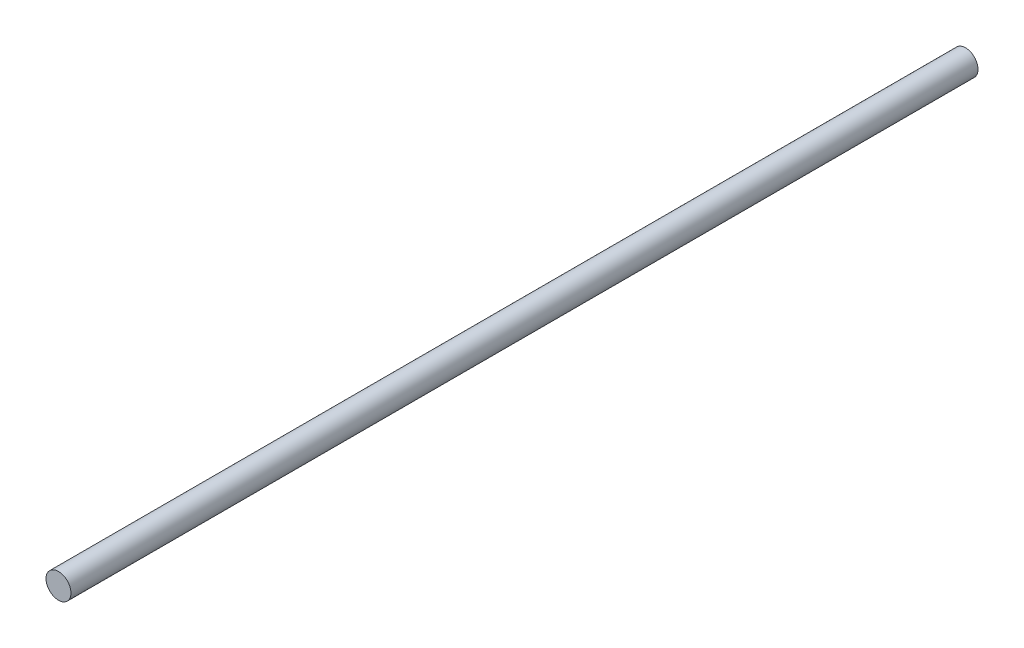
SolidWorks part; units mm, degrees
ref_plane "Front Plane" through (0, 0, 0) normal (0, 0, 1) x (1, 0, 0)
ref_plane "Top Plane" through (0, 0, 0) normal (0, 1, 0) x (1, 0, 0)
ref_plane "Right Plane" through (0, 0, 0) normal (1, 0, 0) x (0, 0, -1)
sketch "Sketch1" plane through (0, 0, 0) normal (0, 0, 1) x (1, 0, 0)
  circle A0 centre (0, 0) radius 2.0955
  dimension "D1" = 4.191
extrude "Boss-Extrude1" add sketch "Sketch1" along normal blind 152.4
